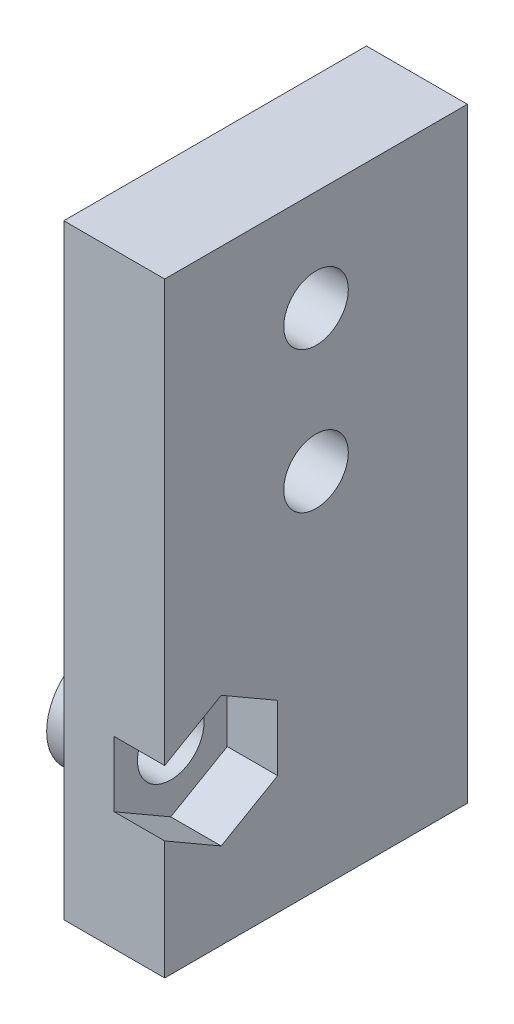
SolidWorks part; units mm, degrees
note: The reader was unsure of these and kept them because the rebuilt part matched: shared geometry of "Sketch1<3>".
ref_plane "Front" through (0, 0, 0) normal (0, 0, 1) x (1, 0, 0)
ref_plane "Top" through (0, 0, 0) normal (0, 1, 0) x (1, 0, 0)
ref_plane "Right" through (0, 0, 0) normal (1, 0, 0) x (0, 0, -1)
sketch "Sketch1" plane through (0, 0, 0) normal (1, 0, 0) x (0, 0, -1)
  line L1 (0, 0) -> (15, 0)
  line L2 (0, 0) -> (0, 30)
  line L3 (0, 30) -> (15, 30)
  line L4 (15, 0) -> (15, 30)
  line L6 (2.8, 4.2668) -> (5.6, 5.8834)
  line L7 (5.6, 5.8834) -> (5.6, 9.1166)
  line L8 (5.6, 9.1166) -> (2.8, 10.7332)
  line L9 (2.8, 10.7332) -> (0, 9.1166)
  line L10 (0, 9.1166) -> (0, 5.8834)
  line L11 (0, 5.8834) -> (2.8, 4.2668)
  circle A0 centre (7.5, 7.5) radius 1.6
  circle A1 centre (7.5, 20) radius 1.6
  circle A2 centre (2.8, 7.5) radius 2.8 construction
  circle A3 centre (7.5, 18) radius 1.6
  circle A4 centre (7.5, 25) radius 1.6
  circle A5 centre (2.8, 7.5) radius 1.65
  dimension "D3" = 7.5
  dimension "D7" = 25
  dimension "D8" = 18
  dimension "D1" = 30
  dimension "D2" = 15
  dimension "D4" = 20
  dimension "D5" = 2.8
  dimension "D6" = 7.5
extrude "Boss-Extrude1" add sketch "Sketch1" along normal blind 2.5
extrude "Boss-Extrude2" add sketch "Sketch1<3>" against normal blind 2.5
sketch "Sketch1<3>" plane through (0, 0, 0) normal (1, 0, 0) x (0, 0, -1) same geometry as "Sketch1"
sketch "Sketch4" plane through (-2.5, 0, 0) normal (-1, 0, 0) x (0, 0, 1)
  circle A0 centre (-2.8, 7.5) radius 1.65
  circle A1 centre (-2.8, 7.5) radius 2.65
extrude "Boss-Extrude3" add sketch "Sketch4" along normal blind 1
